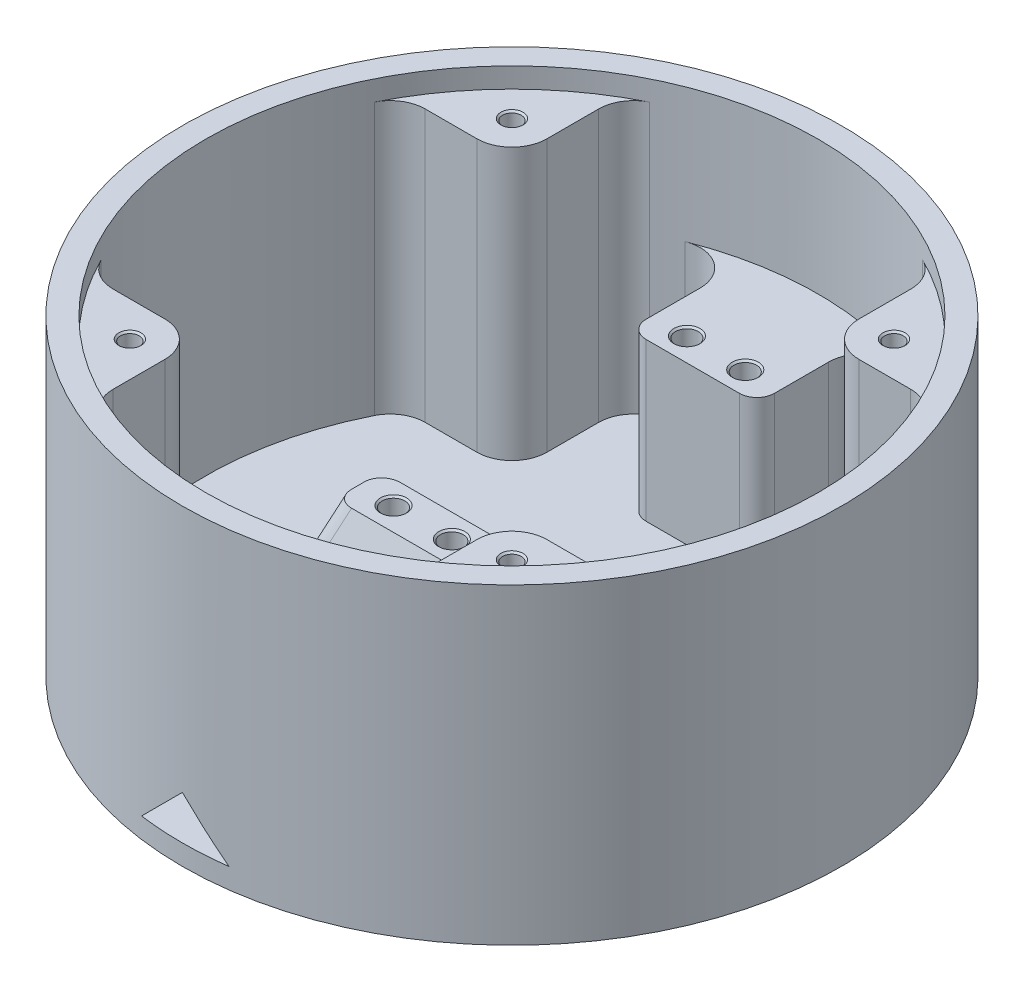
SolidWorks part; units mm, degrees
note: The reader was unsure of these and kept them because the rebuilt part matched: shared geometry of "Sketch1<4>", "Sketch3<3>".
ref_plane "Front Plane" through (0, 0, 0) normal (0, 0, 1) x (1, 0, 0)
ref_plane "Top Plane" through (0, 0, 0) normal (0, 1, 0) x (1, 0, 0)
ref_plane "Right Plane" through (0, 0, 0) normal (1, 0, 0) x (0, 0, -1)
sketch "Sketch1" plane through (0, 0, 0) normal (0, 1, 0) x (1, 0, 0)
  line L0 (0, 0) -> (29628.9875, 0) construction
  line L1 (-11, -21.15) -> (11, -21.15)
  line L2 (-11, -21.15) -> (-11, -29.15)
  line L3 (-11, -29.15) -> (11, -29.15)
  line L4 (11, -21.15) -> (11, -29.15)
  line L5 (-11, -21.15) -> (11, -29.15) construction
  line L6 (-11, -29.15) -> (11, -21.15) construction
  line L7 (-11, 29.15) -> (11, 21.15) construction
  line L8 (-11, 21.15) -> (11, 29.15) construction
  line L9 (11, 21.15) -> (11, 29.15)
  line L10 (-11, 29.15) -> (11, 29.15)
  line L11 (-11, 21.15) -> (-11, 29.15)
  line L12 (-11, 21.15) -> (11, 21.15)
  line L13 (0, 0) -> (0, -50000) construction
  circle A0 centre (-5, -25.15) radius 1.95
  circle A1 centre (5, -25.15) radius 1.95
  circle A2 centre (5, 25.15) radius 1.95
  circle A3 centre (-5, 25.15) radius 1.95
  point P0 (0, -25.15)
  point P12 (0, 25.15)
  point P23 (-5.2171, -25.15)
  point P24 (-15.9079, -25.15)
  point P25 (0, 0)
  point P26 (0, 0)
  dimension "D2" = 3.9
  dimension "D1" = 8
  dimension "D3" = 5
  dimension "D4" = 50.3
  dimension "D5" = 6
extrude "Boss-Extrude1" add sketch "Sketch1" along normal blind 27 contours L11 L12 L9 L10 A2 A3 | A3 | A2 | L4 L1 L2 L3 A0 A1 | A0 | A1
extrude "Boss-Extrude2" add sketch "Sketch1<4>" along normal offset from surface (12 mm away) 15 contours A3 | A2 | A0 | A1 up to face at (0, 27, -25.15)
sketch "Sketch1<4>" plane through (0, 0, 0) normal (0, 1, 0) x (1, 0, 0) same geometry as "Sketch1"
sketch "Sketch3" plane through (0, 0, 0) normal (0, 1, 0) x (1, 0, 0)
  line L0 (-11, -21.15) -> (11, -21.15) construction
  circle A0 centre (0, -9.85) radius 52.5
  circle A1 centre (0, -9.85) radius 56.5
  point P6 (15.4511, -9.85)
  dimension "D2" = 105
  dimension "D1" = 11.3
  dimension "D3" = 4
extrude "Boss-Extrude3" add sketch "Sketch3" against normal blind 3.5 contours A0 | A1 A0
extrude "Boss-Extrude4" add sketch "Sketch3<3>" along normal blind 50
sketch "Sketch3<3>" plane through (0, 0, 0) normal (0, 1, 0) x (1, 0, 0) same geometry as "Sketch3"
sketch "Sketch4" plane through (0, 0, 0) normal (0, 1, 0) x (1, 0, 0)
  line L0 (26.75, 35.324) -> (26.75, 16.9)
  line L1 (26.75, 16.9) -> (45.174, 16.9)
  line L2 (26.75, -36.6) -> (26.75, -55.024)
  line L3 (45.174, -36.6) -> (26.75, -36.6)
  line L4 (-26.75, -36.6) -> (-45.174, -36.6)
  line L5 (-26.75, -55.024) -> (-26.75, -36.6)
  line L6 (-26.75, 16.9) -> (-26.75, 35.324)
  line L7 (-45.174, 16.9) -> (-26.75, 16.9)
  circle A0 centre (0, -9.85) radius 52.5 construction
  circle A1 centre (0, -9.85) radius 52.5 construction
  circle A2 centre (0, -9.85) radius 46.3155 construction
  circle A3 centre (32.75, 22.9) radius 1.6
  circle A4 centre (32.75, -42.6) radius 1.6
  circle A5 centre (-32.75, -42.6) radius 1.6
  circle A6 centre (-32.75, 22.9) radius 1.6
  arc A7 (26.75, 35.324) -> (45.174, 16.9) centre (0, -9.85) cw
  arc A8 (45.174, -36.6) -> (26.75, -55.024) centre (0, -9.85) cw
  arc A9 (-26.75, -55.024) -> (-45.174, -36.6) centre (0, -9.85) cw
  arc A10 (-45.174, 16.9) -> (-26.75, 35.324) centre (0, -9.85) cw
  point P7 (16.9819, -11.891)
  point P8 (0, -9.85)
  point P15 (0, -9.85)
  point P32 (0, -9.85)
  dimension "D5" = 3.2
  dimension "D2" = 65.5
  dimension "D3" = 6
  dimension "D4" = 6
  dimension "D1" = 4
  dimension "D6" = 4
extrude "Boss-Extrude5" add sketch "Sketch4" along normal blind 46.54
sketch "Sketch5" plane through (0, 0, -29.15) normal (0, 0, -1) x (-1, 0, 0)
  line L4 (-11, 0) -> (11, 0)
  line L5 (11, 0) -> (11, 27)
  line L6 (11, 27) -> (-11, 27)
  line L7 (-11, 27) -> (-11, 0)
  line L8 (-11, 0) -> (11, 0)
  line L9 (11, 0) -> (11, 27)
  line L10 (11, 27) -> (-11, 27)
  line L11 (-11, 27) -> (-11, 0)
  dimension "D1" = 0
extrude "Boss-Extrude6" add sketch "Sketch5" along normal up to surface (16.4189 mm away)
fillet "Fillet1" radius 6 14 edges at (-26.75, 23.27, 55.024) (-26.75, 23.27, 36.6) (-45.174, 23.27, 36.6) (26.75, 23.27, 55.024) (45.174, 23.27, 36.6) (26.75, 23.27, 36.6) (45.174, 23.27, -16.9) (26.75, 23.27, -16.9) (26.75, 23.27, -35.324) (-26.75, 23.27, -35.324) (-26.75, 23.27, -16.9) (-45.174, 23.27, -16.9) (-11, 13.5, -41.4847) (11, 13.5, -41.4847)
chamfer "Chamfer1" distance 27 distance2 10 1 edges at (11, 0, 25.15)
chamfer "Chamfer2" distance 10 distance2 27 1 edges at (-11, 0, 25.15)
chamfer "Chamfer3" distance 10 distance2 27 1 edges at (0, 0, 29.15)
sketch "Sketch6" plane through (0, 0, 21.15) normal (0, 0, -1) x (-1, 0, 0)
  line L0 (-7.5, 0) -> (0, 7.5)
  line L1 (0, 7.5) -> (7.5, 0)
  line L2 (-7.5, 0) -> (7.5, 0)
  line L4 (-21, 0) -> (21, 0)
  line L5 (21, 0) -> (11, 27)
  line L6 (11, 27) -> (-11, 27)
  line L7 (-11, 27) -> (-21, 0)
  line L8 (-21, 0) -> (21, 0) construction
  line L9 (21, 0) -> (11, 27) construction
  line L10 (11, 27) -> (-11, 27) construction
  line L11 (-11, 27) -> (-21, 0) construction
  point P7 (0, 0)
  dimension "D2" = 15
  dimension "D1" = 0
extrude "Cut-Extrude2" cut sketch "Sketch6" against normal up to surface (45.2 mm away) up to face at (0, -3.5, 66.35)
chamfer "Chamfer4" distance 5 angle 45 2 edges at (3.75, 3.75, 21.15) (-3.75, 3.75, 21.15)
chamfer "Chamfer5" distance 0.3 angle 45 8 edges at (-32.75, 46.54, 44.2) (-5, 27, 27.1) (32.75, 46.54, 44.2) (32.75, 46.54, -21.3) (-32.75, 46.54, -21.3) (5, 27, -23.2) (5, 27, 23.2) (-5, 27, -27.1)
fillet "Fillet3" radius 3 6 edges at (-16, 13.5, 34.15) (16, 13.5, 34.15) (16, 13.5, 21.15) (-16, 13.5, 21.15) (11, 13.5, -21.15) (-11, 13.5, -21.15)
